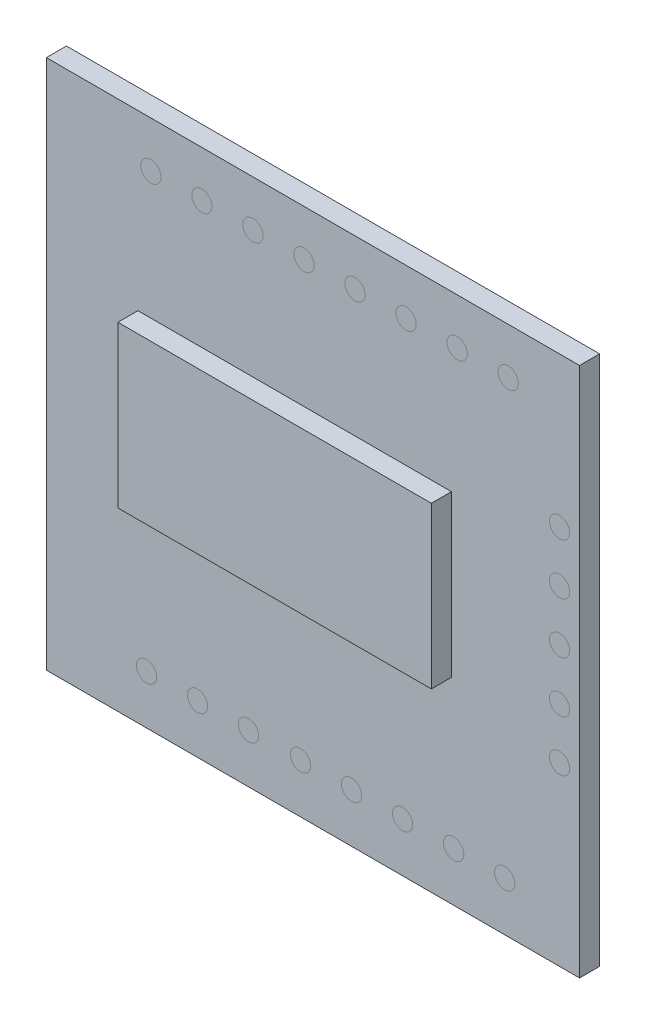
SolidWorks part; units mm, degrees
ref_plane "Front Plane" through (0, 0, 0) normal (0, 0, 1) x (1, 0, 0)
ref_plane "Top Plane" through (0, 0, 0) normal (0, 1, 0) x (1, 0, 0)
ref_plane "Right Plane" through (0, 0, 0) normal (1, 0, 0) x (0, 0, -1)
sketch "Sketch1" plane through (0, 0, 0) normal (0, 0, 1) x (1, 0, 0)
  line L0 (-7.493, -32.0103) -> (602.507, -32.0103) construction
  line L1 (-7.8, 4) -> (7.8, 4)
  line L2 (-7.8, 4) -> (-7.8, -4)
  line L3 (-7.8, -4) -> (7.8, -4)
  line L4 (7.8, 4) -> (7.8, -4)
  line L5 (-7.8, 4) -> (7.8, -4) construction
  line L6 (-7.8, -4) -> (7.8, 4) construction
  line L7 (13.18, 5.1655) -> (13.18, -4.9945) construction
  line L8 (-12.3567, 12.6258) -> (14.1741, 12.6258)
  line L9 (-12.3567, 12.6258) -> (-12.3567, -13.7692)
  line L10 (-12.3567, -13.7692) -> (14.1741, -13.7692)
  line L11 (14.1741, 12.6258) -> (14.1741, -13.7692)
  line L12 (-7.3745, -11.325) -> (10.4495, -11.325) construction
  line L13 (0, 0) -> (25.6443, 0) construction
  line L14 (-7.1565, 10.3285) -> (10.6235, 10.3285) construction
  circle A0 centre (13.18, 5.1655) radius 0.505
  circle A1 centre (13.18, 2.6255) radius 0.505
  circle A2 centre (13.18, 0.0855) radius 0.505
  circle A3 centre (13.18, -2.4545) radius 0.505
  circle A4 centre (13.18, -4.9945) radius 0.505
  circle A5 centre (-7.3745, -11.325) radius 0.505
  circle A6 centre (-4.8345, -11.325) radius 0.505
  circle A7 centre (-2.2945, -11.325) radius 0.505
  circle A8 centre (0.2895, -11.325) radius 0.505
  circle A9 centre (2.8295, -11.325) radius 0.505
  circle A10 centre (5.3695, -11.325) radius 0.505
  circle A11 centre (7.9095, -11.325) radius 0.505
  circle A12 centre (10.4495, -11.325) radius 0.505
  circle A13 centre (-7.1565, 10.3285) radius 0.505
  circle A14 centre (-4.6165, 10.3285) radius 0.505
  circle A15 centre (-2.0765, 10.3285) radius 0.505
  circle A16 centre (0.4635, 10.3285) radius 0.505
  circle A17 centre (3.0035, 10.3285) radius 0.505
  circle A18 centre (5.5435, 10.3285) radius 0.505
  circle A19 centre (8.0835, 10.3285) radius 0.505
  circle A20 centre (10.6235, 10.3285) radius 0.505
  point P0 (0, 0)
  point P56 (0, 0)
  dimension "D3" = 1.01
  dimension "D13" = 1.01
  dimension "D22" = 1.01
  dimension "D1" = 15.6
  dimension "D2" = 8
  dimension "D4" = 13.18
  dimension "D5" = 5.1655
  dimension "D6" = 2.54
  dimension "D7" = 2.54
  dimension "D8" = 2.54
  dimension "D9" = 13.7692
  dimension "D10" = 12.3567
  dimension "D11" = 26.5308
  dimension "D12" = 26.395
  dimension "D14" = 2.54
  dimension "D15" = 2.54
  dimension "D16" = 2.54
  dimension "D17" = 11.325
  dimension "D18" = 7.3745
  dimension "D19" = 2.54
  dimension "D20" = 2.54
  dimension "D21" = 2.54
  dimension "D23" = 2.54
  dimension "D24" = 2.54
  dimension "D25" = 2.54
  dimension "D26" = 2.54
  dimension "D27" = 2.54
  dimension "D28" = 2.54
  dimension "D29" = 2.54
extrude "Boss-Extrude1" add sketch "Sketch1" against normal blind 1 contours L8 L11 L10 L9
extrude "Cut-Extrude1" cut sketch "Sketch1<4>" against normal blind 1 contours A13 | A14 | A15 | A16 | A17 | A18 | A19 | A20 | A0 | A2 | A3 | A4 | A12 | A11 | A10 | A9 | A8 | A6 | A5 | A1 | A7 region at (13.18, 5.1655, 0) region at (13.18, 0.0855, 0) region at (13.18, -2.4545, 0) region at (13.18, -4.9945, 0) region at (-7.3745, -11.325, 0) region at (-4.8345, -11.325, 0) region at (0.2895, -11.325, 0) region at (2.8295, -11.325, 0) region at (5.3695, -11.325, 0) region at (7.9095, -11.325, 0) region at (10.4495, -11.325, 0) region at (-7.1565, 10.3285, 0) region at (-4.6165, 10.3285, 0) region at (-2.0765, 10.3285, 0) region at (0.4635, 10.3285, 0) region at (3.0035, 10.3285, 0) region at (5.5435, 10.3285, 0) region at (8.0835, 10.3285, 0) region at (10.6235, 10.3285, 0)
sketch "Sketch1<4>" plane through (0, 0, 0) normal (0, 0, 1) x (1, 0, 0) same geometry as "Sketch1"
extrude "Boss-Extrude2" add sketch "Sketch1<3>" against normal blind 1 separate body contours A13 | A14 | A16 | A17 | A18 | A19 | A20 | A0 | A3 | A4 | A5 | A7 | A8 | A9 | A11 | A12 | A15 | A1 | A2 | A6 | A10 region at (13.18, 5.1655, 0) region at (13.18, -2.4545, 0) region at (13.18, -4.9945, 0) region at (-7.3745, -11.325, 0) region at (-2.2945, -11.325, 0) region at (0.2895, -11.325, 0) region at (2.8295, -11.325, 0) region at (7.9095, -11.325, 0) region at (10.4495, -11.325, 0) region at (-7.1565, 10.3285, 0) region at (-4.6165, 10.3285, 0) region at (0.4635, 10.3285, 0) region at (3.0035, 10.3285, 0) region at (5.5435, 10.3285, 0) region at (8.0835, 10.3285, 0) region at (10.6235, 10.3285, 0)
sketch "Sketch1<3>" plane through (0, 0, 0) normal (0, 0, 1) x (1, 0, 0) same geometry as "Sketch1"
extrude "Boss-Extrude3" add sketch "Sketch1<5>" along normal blind 1 contours L4 L1 L2 L3 region at (0, 0, 0)
sketch "Sketch1<5>" plane through (0, 0, 0) normal (0, 0, 1) x (1, 0, 0) same geometry as "Sketch1"
